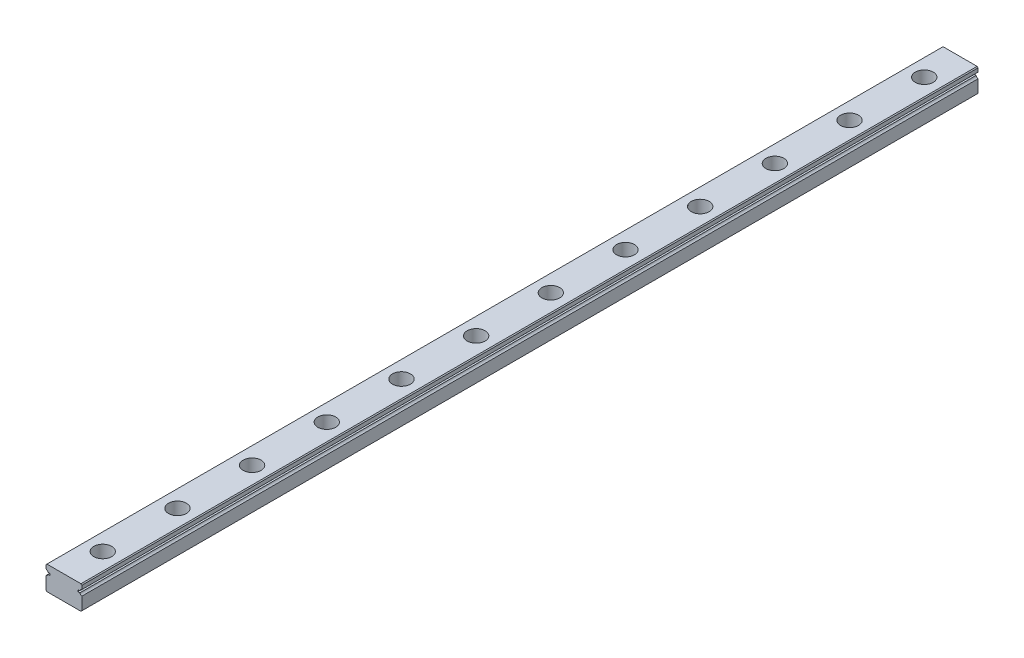
SolidWorks part; units mm, degrees
ref_plane "Спереди" through (0, 0, 0) normal (0, 0, 1) x (1, 0, 0)
ref_plane "Сверху" through (0, 0, 0) normal (0, 1, 0) x (1, 0, 0)
ref_plane "Справа" through (0, 0, 0) normal (1, 0, 0) x (0, 0, -1)
sketch "Эскиз1" plane through (0, 0, 0) normal (0, 0, 1) x (1, 0, 0)
  line L0 (-6, 3.7) -> (-5.7, 4)
  line L1 (-5.7, -4) -> (5.7, -4)
  line L2 (-6, -3.7) -> (-6, 0.549)
  line L3 (-5.7, 4) -> (5.7, 4)
  line L4 (6, -3.7) -> (6, 0.549)
  line L5 (-6, -4) -> (6, 4) construction
  line L6 (-6, 4) -> (6, -4) construction
  line L7 (-6, -3.7) -> (-5.7, -4)
  line L8 (5.7, -4) -> (6, -3.7)
  line L9 (5.7, 4) -> (6, 3.7)
  line L10 (-6, 2.451) -> (-6, 3.7)
  line L11 (-5.3546, 1.7981) -> (-4.6435, 1.7981)
  line L12 (0, 5.4188) -> (0, -5.747) construction
  line L13 (-5.3546, 1.2019) -> (-4.6435, 1.2019)
  line L14 (-4.6435, 1.7981) -> (-4.6435, 1.2019)
  line L15 (4.6435, 1.7981) -> (4.6435, 1.2019)
  line L16 (5.3546, 1.2019) -> (4.6435, 1.2019)
  line L17 (5.3546, 1.7981) -> (4.6435, 1.7981)
  line L18 (6, 2.451) -> (6, 3.7)
  line L19 (4.6435, 1.7981) -> (5.3546, 1.7981) construction
  arc A0 (-6, 0.549) -> (-5.3546, 1.2019) centre (-6.3091, 1.5) ccw
  arc A1 (-5.3546, 1.7981) -> (-6, 2.451) centre (-6.3091, 1.5) ccw
  arc A2 (5.3546, 1.7981) -> (6, 2.451) centre (6.3091, 1.5) cw
  arc A3 (6, 0.549) -> (5.3546, 1.2019) centre (6.3091, 1.5) cw
  point P0 (0, 0)
extrude "Бобышка-Вытянуть1" add sketch "Эскиз1" along normal blind 300
sketch "Эскиз2" plane through (0, 4, 0) normal (0, 1, 0) x (1, 0, 0)
  line L0 (0, 0) -> (0, -26.2396) construction
  line L1 (5.7, 0) -> (-5.7, 0) construction
  line L2 (-3.8306, -12) -> (3.8306, -12) construction
  circle A0 centre (0, -12) radius 3
  circle A1 centre (0, -12) radius 1.75
  dimension "D2" = 3.5
  dimension "D3" = 6
  dimension "D1" = 12
extrude "Вырез-Вытянуть1" cut sketch "Эскиз2" against normal blind 4.5
extrude "Вырез-Вытянуть2" cut sketch "Эскиз2<2>" against normal through all contours A1 region at (0, 4, 12)
sketch "Эскиз2<2>" plane through (0, 4, 0) normal (0, 1, 0) x (1, 0, 0) same geometry as "Эскиз2"
pattern_linear "Линейный массив1" count 16 spacing 25 along (0, 0, 1) of "Вырез-Вытянуть1", "Вырез-Вытянуть2"
